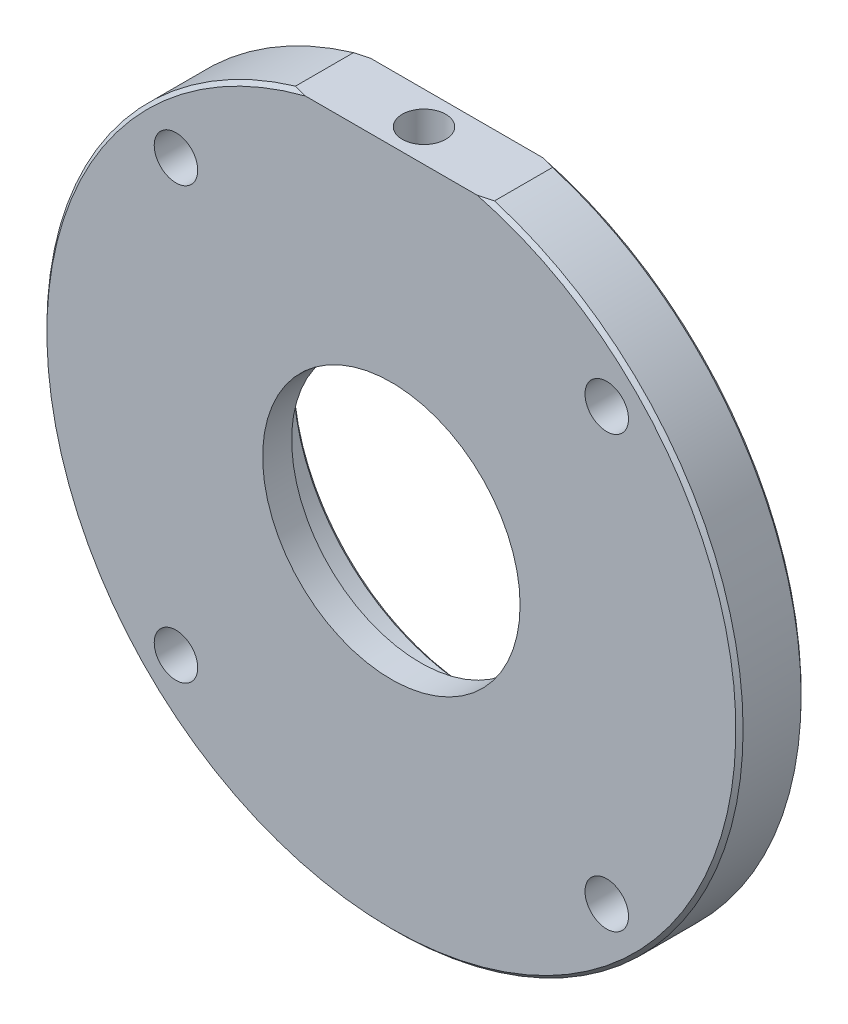
SolidWorks part; units mm, degrees
ref_plane "Front Plane" through (0, 0, 0) normal (0, 0, 1) x (1, 0, 0)
ref_plane "Top Plane" through (0, 0, 0) normal (0, 1, 0) x (1, 0, 0)
ref_plane "Right Plane" through (0, 0, 0) normal (1, 0, 0) x (0, 0, -1)
sketch "Sketch1" plane through (0, 0, 0) normal (1, 0, 0) x (0, 0, -1)
  line L0 (0, 0) -> (24.537, 0) construction
  line L1 (0, 17.75) -> (0, 48)
  line L2 (0, 48) -> (9, 48)
  line L3 (9, 48) -> (9, 36)
  line L4 (9, 36) -> (14, 36)
  line L5 (14, 36) -> (14, 30)
  line L6 (14, 30) -> (12, 30)
  line L7 (12, 30) -> (12, 25)
  line L8 (12, 25) -> (4, 25)
  line L9 (4, 25) -> (4, 17.75)
  line L10 (4, 17.75) -> (0, 17.75)
  dimension "D1" = 14
  dimension "D2" = 10
  dimension "D3" = 2
  dimension "D4" = 5
  dimension "D5" = 96
  dimension "D6" = 35.5
  dimension "D7" = 50
  dimension "D8" = 60
  dimension "D9" = 72
revolve "Revolve1" add sketch "Sketch1" angle 360 about L0
sketch "Sketch2" plane through (0, 0, -9) normal (0, 0, -1) x (-1, 0, 0)
  line L0 (0, 0) -> (10.4544, 0) construction
  line L1 (0, 0) -> (29.6985, 29.6985) construction
  line L2 (-13.7113, 46) -> (13.7113, 46)
  circle A0 centre (0, 0) radius 42 construction
  circle A1 centre (29.6985, 29.6985) radius 3
  circle A2 centre (29.6985, -29.6985) radius 3
  circle A3 centre (-29.6985, -29.6985) radius 3
  circle A4 centre (-29.6985, 29.6985) radius 3
  circle A5 centre (0, 0) radius 48 construction
  arc A6 (13.7113, 46) -> (-13.7113, 46) centre (0, 0) ccw
  point P6 (0, 0)
  point P15 (0, 0)
  point P18 (0, 0)
  point P19 (0, 0)
  point P20 (29.6985, -29.6985)
  point P21 (-29.6985, -29.6985)
  point P22 (29.6985, 29.6985)
  dimension "D1" = 84
  dimension "D2" = 6
  dimension "D3" = 45
  dimension "D5" = 46
  dimension "D4" = 4
extrude "Cut-Extrude1" cut sketch "Sketch2" against normal through all
hole_wizard "Ø3.0mm Dowel Hole1" positions "Sketch4" profile "Sketch5" hole size "Ø3.0" standard "ANSI Metric"
sketch "Sketch4" plane through (0, 0, -12) normal (0, 0, -1) x (-1, 0, 0)
  line L0 (-13.7113, 46) -> (13.7113, 46) construction
  point P0 (0, 28)
  dimension "D1" = 18
sketch "Sketch5" plane through (0, 28, -12) normal (1, 0, 0) x (0, 1, 0)
  line L0 (0, 0) -> (0, 11)
  line L1 (0, 11) -> (1.5, 10.0987)
  line L2 (1.5, 10.0987) -> (1.5, 0)
  line L5 (1.5, 0) -> (0, 0)
  line L10 (0, 11) -> (-1.5, 10.0987) construction
  line L11 (0, -6.35) -> (0, 107.95) construction
  dimension "Hole Dia." = 3
  dimension "Hole Depth" = 11
  dimension "Drill Angle" = 118
hole_wizard "CBORE for M6 Hex Head Bolt1" positions "Sketch7" profile "Sketch8" counterbore size "M6" standard "ANSI Metric" end condition up to next
sketch "Sketch7" plane through (0, 46, 0) normal (0, 1, 0) x (1, 0, 0)
  point P0 (0, 4.5)
  point P4 (58.7656, 2.6143)
  dimension "D1" = 4.5
sketch "Sketch8" plane through (0, 46, -4.5) normal (1, 0, 0) x (0, 0, 1)
  line L0 (0, 0) -> (0, 16.5)
  line L1 (0, 16.5) -> (1.5, 16.5)
  line L3 (1.5, 16.5) -> (1.5, 7)
  line L4 (1.5, 7) -> (3, 7)
  line L5 (3, 7) -> (3, 0)
  line L7 (3, 0) -> (0, 0)
  line L11 (0, -6.35) -> (0, 107.95) construction
  dimension "Thru Hole Dia." = 3
  dimension "Thru Hole Depth" = 16.5
  dimension "C'Bore Dia." = 6
  dimension "C'Bore Depth" = 7
chamfer "Chamfer1" distance 0.5 angle 45 4 edges at (0, -48, 0) (0, -48, -9) (25, 0, -12) (36, 0, -14)
